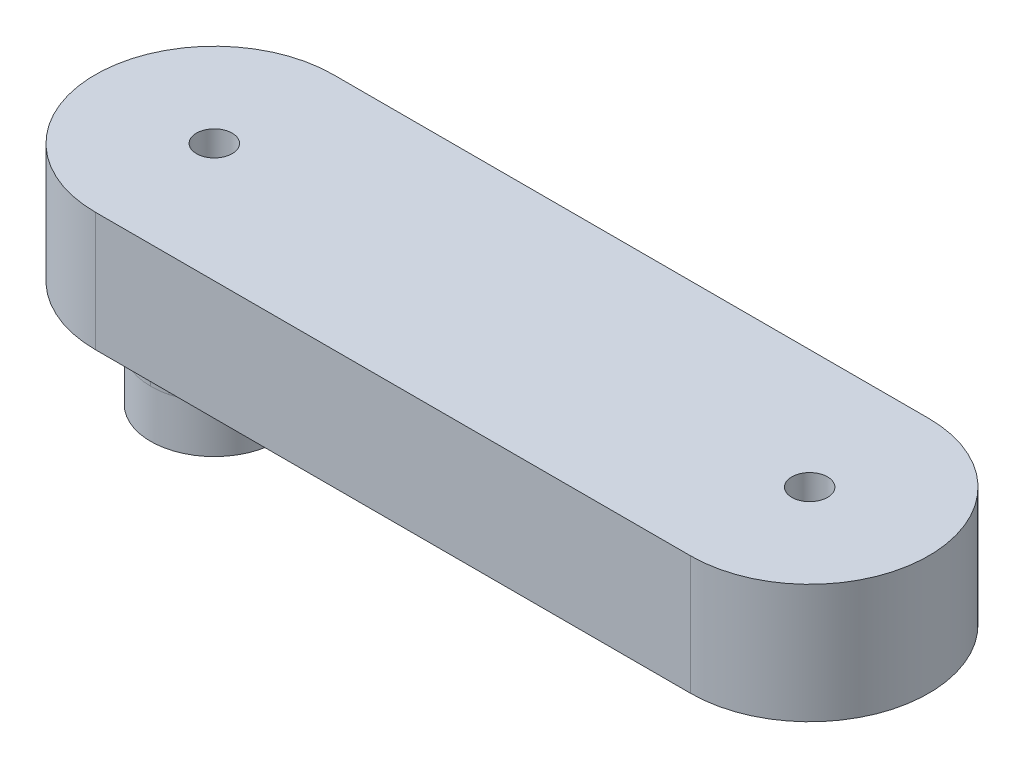
SolidWorks part; units mm, degrees
ref_plane "Front Plane" through (0, 0, 0) normal (0, 0, 1) x (1, 0, 0)
ref_plane "Top Plane" through (0, 0, 0) normal (0, 1, 0) x (1, 0, 0)
ref_plane "Right Plane" through (0, 0, 0) normal (1, 0, 0) x (0, 0, -1)
sketch "Sketch1" plane through (0, 0, 0) normal (0, 1, 0) x (1, 0, 0)
  line L0 (-25, 0) -> (25, 0) construction
  line L1 (-25, 10) -> (25, 10)
  line L2 (-25, -10) -> (25, -10)
  arc A0 (-25, 10) -> (-25, -10) centre (-25, 0) ccw
  arc A1 (25, -10) -> (25, 10) centre (25, 0) ccw
  point P3 (0, 0)
  dimension "D1" = 10
  dimension "D2" = 50
extrude "Boss-Extrude1" add sketch "Sketch1" along normal blind 10
sketch "Sketch2" plane through (0, 10, 0) normal (0, 1, 0) x (1, 0, 0)
  circle A5 centre (25, 0) radius 1.5
  dimension "D1" = 3
extrude "Cut-Extrude1" cut sketch "Sketch2" against normal up to next
sketch "Sketch5" plane through (0, 0, 0) normal (0, -1, 0) x (1, 0, 0)
  circle A0 centre (-25, 0) radius 5.35
  dimension "D1" = 10.7
extrude "Boss-Extrude3" add sketch "Sketch5" along normal blind 9
fillet "Fillet1" radius 5 1 edges at (-25, 0, 5.35)
sketch "Sketch6" plane through (0, -9, 0) normal (0, -1, 0) x (-1, 0, 0)
  circle A0 centre (25, 0) radius 1.5
  dimension "D1" = 3
extrude "Cut-Extrude2" cut sketch "Sketch6" against normal up to next
equation "\"Length\"= 50mm"
equation "\"Radius\"= 10mm"
equation "\"D1@Sketch1\"= \"Radius\""
equation "\"D2@Sketch1\" = \"Length\""
equation "\"Thick\"= 10mm"
equation "\"D1@Boss-Extrude1\"= \"Thick\""
